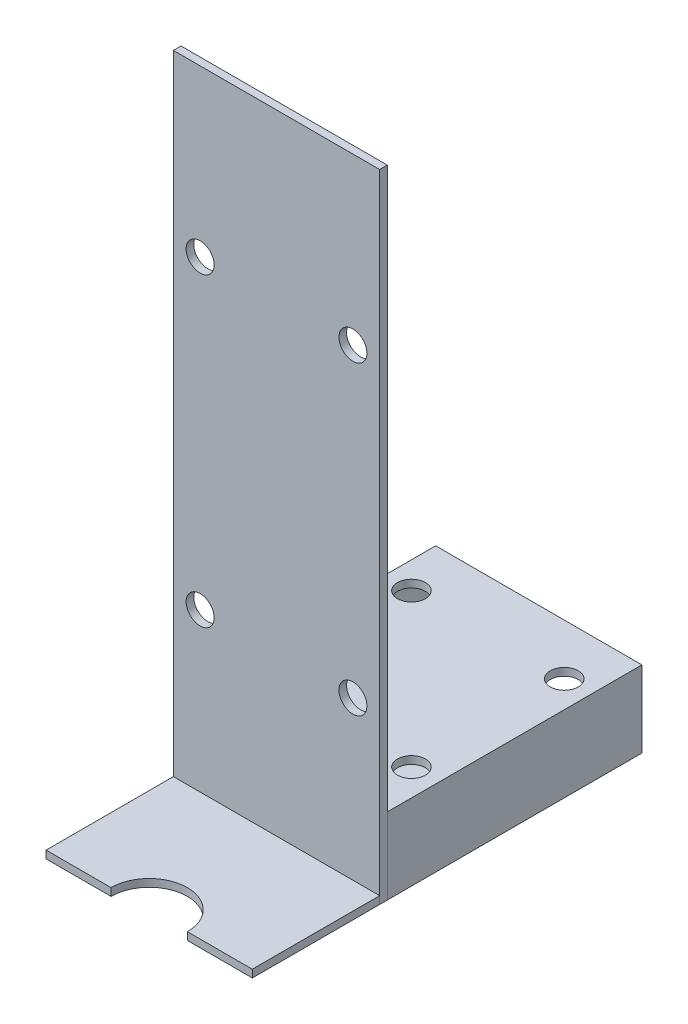
SolidWorks part; units mm, degrees
material "ASTM A36 Steel"
ref_plane "Front Plane" through (0, 0, 0) normal (0, 0, 1) x (1, 0, 0)
ref_plane "Top Plane" through (0, 0, 0) normal (0, 1, 0) x (1, 0, 0)
ref_plane "Right Plane" through (0, 0, 0) normal (1, 0, 0) x (0, 0, -1)
sketch "Sketch2" plane through (0, 0, 0) normal (0, 0, 1) x (1, 0, 0)
  line L1 (0, 0) -> (37.5, 0)
  line L2 (0, 0) -> (0, 12)
  line L3 (0, 12) -> (37.5, 12)
  line L4 (37.5, 0) -> (37.5, 12)
  dimension "D1" = 37.5
  dimension "D2" = 12
extrude "tube cantilever" add sketch "Sketch2" along normal blind 50 thin thin type one direction wall 1.5
sketch "Sketch4" plane through (0, -1.5, 0) normal (0, 1, 0) x (1, 0, 0)
  line L0 (39, -50) -> (39, 0) construction
  line L1 (-1.5, -50) -> (39, -50)
  line L2 (-1.5, -50) -> (-1.5, -51.5)
  line L3 (-1.5, -51.5) -> (39, -51.5)
  line L4 (39, -50) -> (39, -51.5)
  dimension "D1" = 1.5
extrude "flange leg" add sketch "Sketch4" along normal blind 125 separate body
sketch "Sketch5" plane through (0, 0, 51.5) normal (0, 0, 1) x (1, 0, 0)
  line L0 (39, 123.5) -> (39, -1.5) construction
  line L1 (-1.5, -1.5) -> (39, -1.5)
  line L2 (-1.5, -1.5) -> (-1.5, 0)
  line L3 (-1.5, 0) -> (39, 0)
  line L4 (39, -1.5) -> (39, 0)
  dimension "D1" = 1.5
extrude "bottom leg" add sketch "Sketch5" along normal blind 25 separate body
sketch "Sketch6" plane through (0, -1.5, 0) normal (0, -1, 0) x (1, 0, 0)
  line L0 (-1.5, 76.5) -> (39, 76.5) construction
  circle A0 centre (18.75, 76.5) radius 7.5
  dimension "D1" = 15
extrude "leadscrew clearance" cut sketch "Sketch6" against normal blind 25
hole_wizard "desktop hole pattern" positions "Sketch7" profile "Sketch8" hole size "M5" standard "ANSI Metric" end condition through all
sketch "Sketch7" plane through (0, 13.5, 0) normal (0, 1, 0) x (1, 0, 0)
  line L1 (3.75, -10) -> (33.75, -10)
  line L2 (3.75, -10) -> (3.75, -40)
  line L3 (3.75, -40) -> (33.75, -40)
  line L4 (33.75, -10) -> (33.75, -40)
  line L5 (18.75, -10) -> (18.75, 0)
  line L6 (39, 0) -> (-1.5, 0) construction
  line L8 (33.75, -25) -> (39, -25)
  line L9 (39, -50) -> (39, 0) construction
  point P1 (3.75, -10)
  point P2 (33.75, -40)
  point P117 (3.75, -40)
  point P118 (33.75, -10)
  dimension "D1" = 30
  dimension "D2" = 30
sketch "Sketch8" plane through (3.75, 13.5, 10) normal (1, 0, 0) x (0, 0, 1)
  line L0 (0, 0) -> (0, 15)
  line L1 (0, 15) -> (2.75, 15)
  line L2 (2.75, 15) -> (2.75, 0)
  line L5 (2.75, 0) -> (0, 0)
  line L11 (0, -6.35) -> (0, 107.95) construction
  dimension "Thru Hole Dia." = 5.5
  dimension "Thru Hole Depth" = 15
hole_wizard "bearing hole pattern" positions "Sketch9" profile "Sketch10" hole size "M5" standard "ANSI Metric" end condition through all
sketch "Sketch9" plane through (0, 0, 50) normal (0, 0, -1) x (-1, 0, 0)
  line L6 (-33.75, 91) -> (-3.75, 91)
  line L7 (-33.75, 91) -> (-33.75, 31)
  line L8 (-33.75, 31) -> (-3.75, 31)
  line L9 (-3.75, 91) -> (-3.75, 31)
  line L10 (-18.75, 91) -> (-18.75, 123.5)
  line L11 (-39, 123.5) -> (1.5, 123.5) construction
  line L13 (-3.75, 61) -> (1.5, 61)
  line L14 (1.5, 123.5) -> (1.5, -1.5) construction
  point P12 (-33.75, 91)
  point P13 (-3.75, 31)
  point P82 (-33.75, 31)
  point P83 (-3.75, 91)
  dimension "D1" = 60
  dimension "D2" = 30
sketch "Sketch10" plane through (33.75, 91, 50) normal (1, 0, 0) x (0, 1, 0)
  line L0 (0, 0) -> (0, 26.5)
  line L1 (0, 26.5) -> (2.75, 26.5)
  line L2 (2.75, 26.5) -> (2.75, 0)
  line L5 (2.75, 0) -> (0, 0)
  line L11 (0, -6.35) -> (0, 107.95) construction
  dimension "Thru Hole Dia." = 5.5
  dimension "Thru Hole Depth" = 26.5
ref_axis "y axis" through (39, 13.5, 0) along (-1, 0, 0)
ref_axis "x axis" through (39, 13.5, 50) along (0, 0, -1)
equation "\"sheet_thicknes\"=1.5"
equation "\"D1@Sketch4\"=\"sheet_thicknes\""
equation "\"D1@Sketch5\"=\"sheet_thicknes\""
